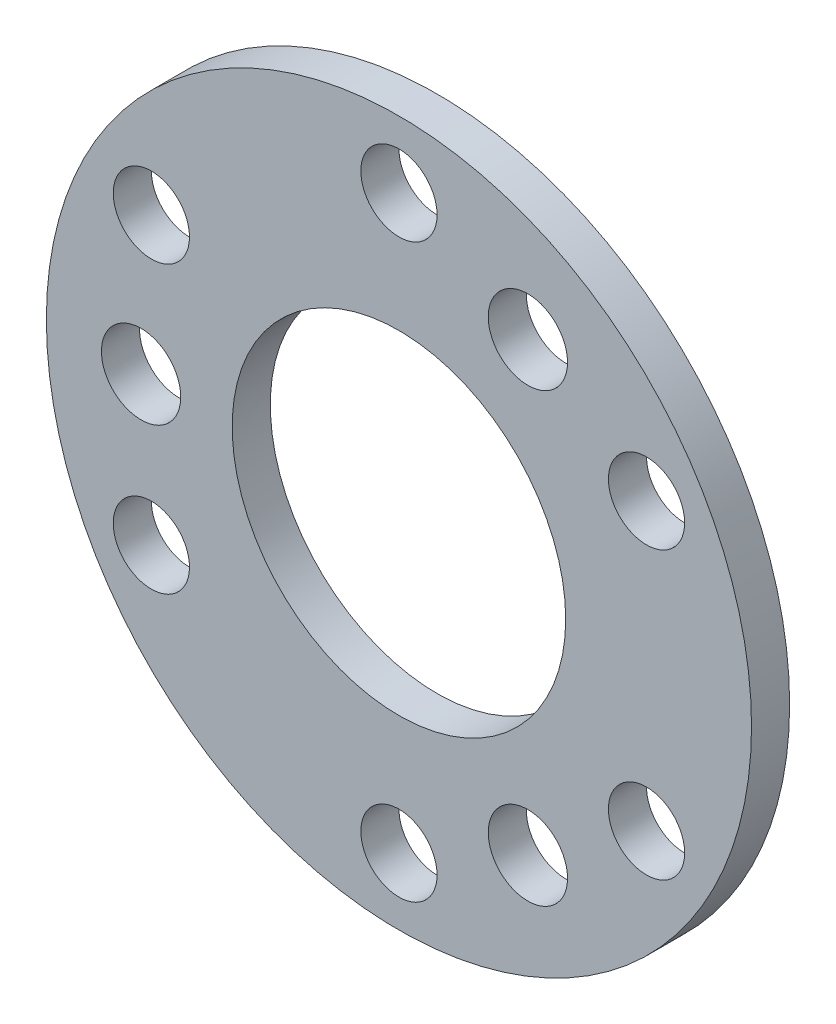
SolidWorks part; units mm, degrees
ref_plane "前视基准面" through (0, 0, 0) normal (0, 0, 1) x (1, 0, 0)
ref_plane "上视基准面" through (0, 0, 0) normal (0, 1, 0) x (1, 0, 0)
ref_plane "右视基准面" through (0, 0, 0) normal (1, 0, 0) x (0, 0, -1)
sketch "草图1" plane through (0, 0, 0) normal (0, 0, 1) x (1, 0, 0)
  line L0 (-0.9852, 0.129) -> (-0.9852, -3.2208) construction
  circle A0 centre (-0.9852, 0.129) radius 15 construction
  circle A1 centre (-0.9852, 0.129) radius 13.53 construction
  circle A2 centre (-0.9852, -14.871) radius 2
  circle A3 centre (-13.9756, -7.371) radius 2
  circle A4 centre (-13.9756, 7.629) radius 2
  circle A5 centre (-0.9852, 15.129) radius 2
  circle A6 centre (12.0052, 7.629) radius 2
  circle A7 centre (12.0052, -7.371) radius 2
  circle A8 centre (-14.5152, 0.129) radius 2.08
  circle A9 centre (5.7798, 11.8463) radius 2.08
  circle A10 centre (5.7798, -11.5883) radius 2.08
  circle A11 centre (-0.9852, 0.129) radius 8.75
  circle A12 centre (-0.9852, 0.129) radius 18.5
extrude "凸台-拉伸1" add sketch "草图1" along normal blind 2
sketch "草图2" plane through (0, 0, 0) normal (0, 0, -1) x (-1, 0, 0)
  line L0 (0.9852, 0.129) -> (0.9852, -8.621) construction
  circle A0 centre (0.9852, 0.129) radius 8.75 construction
sketch "草图3" plane through (0, 0, 0) normal (0, 0, -1) x (-1, 0, 0)
  circle A0 centre (0.9852, 0.129) radius 5
sketch "草图4" plane through (0, 0, 2) normal (0, 0, 1) x (1, 0, 0)
  circle A1 centre (-0.9852, 0.129) radius 5
